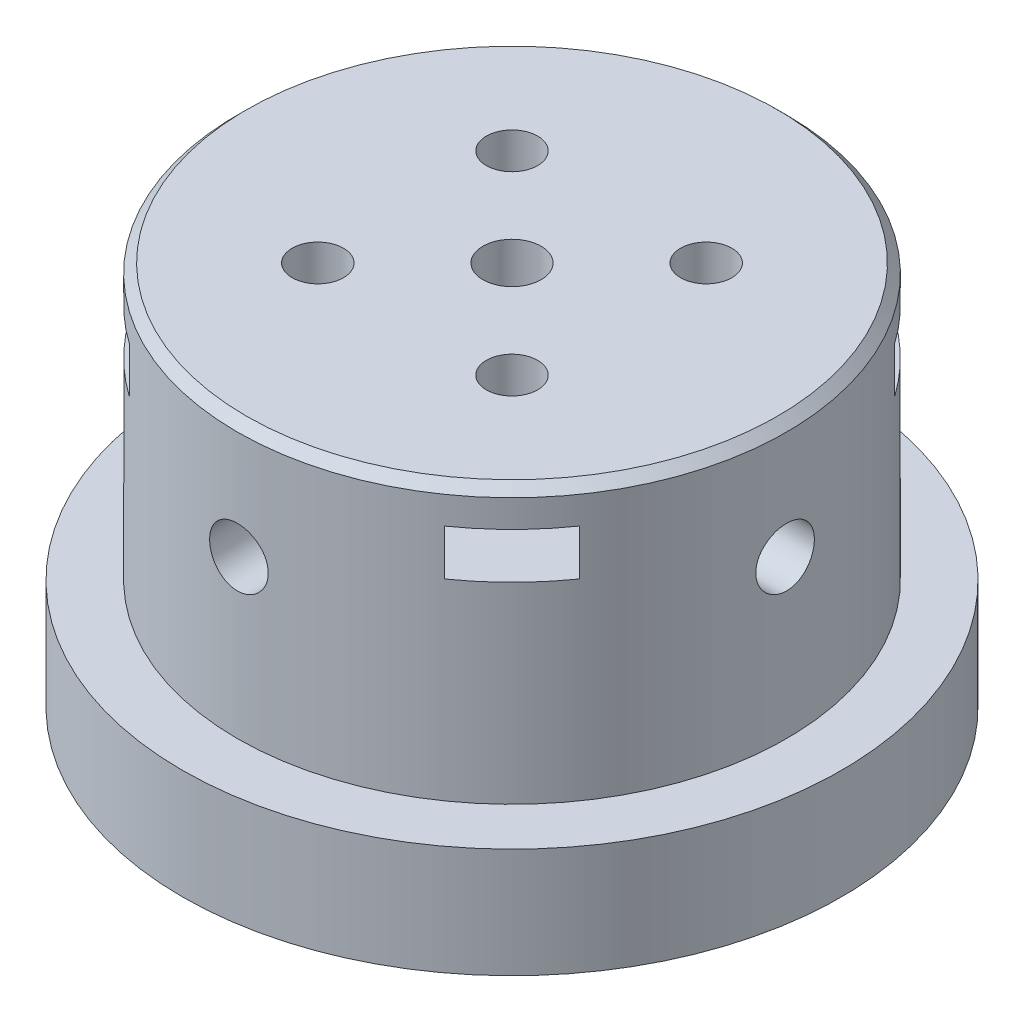
SolidWorks part; units mm, degrees
ref_plane "Front Plane" through (0, 0, 0) normal (0, 0, 1) x (1, 0, 0)
ref_plane "Top Plane" through (0, 0, 0) normal (0, 1, 0) x (1, 0, 0)
ref_plane "Right Plane" through (0, 0, 0) normal (1, 0, 0) x (0, 0, -1)
sketch "Sketch1" plane through (0, 0, 0) normal (0, 1, 0) x (1, 0, 0)
  circle A0 centre (0, 0) radius 15
  dimension "D1" = 30
extrude "Boss-Extrude1" add sketch "Sketch1" along normal blind 2
sketch "Sketch2" plane through (0, 2, 0) normal (0, 1, 0) x (1, 0, 0)
  circle A0 centre (0, 0) radius 13.5
  circle A1 centre (0, 0) radius 15
  circle A2 centre (0, 0) radius 15
  dimension "D1" = 0
  dimension "D2" = 1.5
extrude "Boss-Extrude2" add sketch "Sketch2" against normal up to surface (15 mm away)
sketch "Sketch3" plane through (0, -13, 0) normal (0, -1, 0) x (1, 0, 0)
  circle A0 centre (0, 0) radius 13.5 construction
  circle A1 centre (0, 0) radius 13.5
  circle A2 centre (0, 0) radius 18
  dimension "D1" = 36
extrude "Boss-Extrude3" add sketch "Sketch3" along normal up to surface (2 mm away)
sketch "Sketch4" plane through (0, -15, 0) normal (0, -1, 0) x (1, 0, 0)
  circle A0 centre (0, 0) radius 16.1
  circle A1 centre (0, 0) radius 18
  circle A2 centre (0, 0) radius 18
  dimension "D2" = 32.2
  dimension "D1" = 0
extrude "Boss-Extrude4" add sketch "Sketch4" along normal up to surface (3.9878 mm away)
chamfer "Chamfer1" distance 1 angle 45 1 edges at (0, -15, 13.5)
sketch "Sketch5" plane through (0, 2, 0) normal (0, 1, 0) x (1, 0, 0)
  circle A0 centre (0, 0) radius 13.5
  circle A1 centre (0, 0) radius 13.5 construction
extrude "Boss-Extrude5" add sketch "Sketch5" against normal up to surface (10.8258 mm away)
sketch "Sketch6" plane through (0, 2, 0) normal (0, 1, 0) x (1, 0, 0)
  circle A0 centre (0, 0) radius 1.5875
  dimension "D1" = 3.175
extrude "Cut-Extrude1" cut sketch "Sketch6" against normal through all both and the other way through all
sketch "Sketch7" plane through (0, 0, 0) normal (1, 0, 0) x (0, 0, -1)
  line L0 (0, 0) -> (0, -8.8258) construction
  line L1 (-1.5875, -8.8258) -> (1.5875, -8.8258) construction
  circle A0 centre (0, -4.4129) radius 1.6
  dimension "D1" = 3.2
extrude "Cut-Extrude2" cut sketch "Sketch7" against normal through all
ref_axis "Axis1" through (0, -14, 0) along (0, 1, 0)
ref_plane "Plane2" through (-10, 0, 0) normal (1, 0, 0) x (0, 0, -1)
ref_plane "Plane3" through (-9, 0, 0) normal (1, 0, 0) x (0, 0, -1)
sketch "Sketch11" plane through (-10, 0, 0) normal (1, 0, 0) x (0, 0, -1)
  circle A0 centre (0, -4.4129) radius 1.6 construction
  circle A1 centre (0, -4.4129) radius 1.6 construction
  circle A2 centre (0, -4.4129) radius 2
  dimension "D1" = 4
extrude "Cut-Extrude7" [suppressed] cut sketch "Sketch11" along normal blind 5.5
sketch "Sketch12" plane through (-10, 0, 0) normal (1, 0, 0) x (0, 0, -1)
  circle A0 centre (0, -4.4129) radius 3.5
  dimension "D1" = 7
extrude "Cut-Extrude8" [suppressed] cut sketch "Sketch12" against normal blind 5
chamfer "Chamfer2" [suppressed] distance 1 angle 45
pattern_circular "CirPattern3" count 4 over 360 about axis through (0, -14, 0) along (0, 1, 0) of "Cut-Extrude2", "Cut-Extrude7", "Cut-Extrude8", "Chamfer2"
sketch "Sketch13" plane through (-9, 0, 0) normal (1, 0, 0) x (0, 0, -1)
  line L0 (-2.75, -6.0006) -> (-2.75, -8.8258)
  line L1 (0, -7.5883) -> (2.75, -6.0006) construction
  line L2 (2.75, -6.0006) -> (2.75, -2.8252)
  line L3 (2.75, -2.8252) -> (0, -1.2375)
  line L4 (0, -1.2375) -> (-2.75, -2.8252)
  line L5 (-2.75, -2.8252) -> (-2.75, -6.0006)
  line L6 (-2.75, -6.0006) -> (0, -7.5883) construction
  line L7 (-2.75, -8.8258) -> (2.75, -8.8258)
  line L8 (2.75, -8.8258) -> (2.75, -6.0006)
  line L9 (-1.5875, -8.8258) -> (1.5875, -8.8258) construction
  circle A0 centre (0, -4.4129) radius 2.75 construction
  circle A1 centre (0, -4.4129) radius 1.6 construction
  dimension "D1" = 5.5
extrude "Cut-Extrude9" cut sketch "Sketch13" along normal blind 3
pattern_circular "CirPattern4" count 4 over 360 about axis through (0, -14, 0) along (0, 1, 0) of "Cut-Extrude9"
sketch "Sketch14" plane through (0, 2, 0) normal (0, -1, 0) x (1, 0, 0)
  line L0 (0, 0) -> (0, 13.5) construction
  line L1 (0, 0) -> (-9.5459, 9.5459) construction
  circle A0 centre (0, 0) radius 13.5 construction
  circle A1 centre (-5.3033, 5.3033) radius 1.4
  circle A2 centre (5.3033, 5.3033) radius 1.4
  circle A3 centre (5.3033, -5.3033) radius 1.4
  circle A4 centre (-5.3033, -5.3033) radius 1.4
  point P18 (0, 0)
  dimension "D3" = 2.8
  dimension "D1" = 45
  dimension "D2" = 7.5
  dimension "D4" = 4
extrude "Cut-Extrude10" cut sketch "Sketch14" along normal blind 4.5 and the other way through all
ref_plane "Plane4" through (0, 0, 0) normal (0, 1, 0) x (1, 0, 0)
sketch "Sketch15" plane through (0, 0, 0) normal (0, 1, 0) x (1, 0, 0)
  line L0 (0, 0) -> (-10.6066, 10.6066) construction
  line L1 (-8.2032, 4.5263) -> (-12.4451, 8.7681)
  line L2 (-7.4262, 7.4262) -> (-8.2032, 4.5263) construction
  line L3 (-8.2032, 4.5263) -> (-6.0803, 2.4034)
  line L4 (-6.0803, 2.4034) -> (-3.1804, 3.1804)
  line L5 (-3.1804, 3.1804) -> (-2.4034, 6.0803)
  line L6 (-2.4034, 6.0803) -> (-4.5263, 8.2032)
  line L7 (-4.5263, 8.2032) -> (-7.4262, 7.4262) construction
  line L8 (-12.4451, 8.7681) -> (-8.7681, 12.4451)
  line L9 (-8.7681, 12.4451) -> (-4.5263, 8.2032)
  line L10 (12.4451, 8.7681) -> (8.2032, 4.5263)
  line L11 (6.0803, 2.4034) -> (8.2032, 4.5263)
  line L12 (3.1804, 3.1804) -> (6.0803, 2.4034)
  line L13 (2.4034, 6.0803) -> (3.1804, 3.1804)
  line L14 (4.5263, 8.2032) -> (2.4034, 6.0803)
  line L15 (4.5263, 8.2032) -> (8.7681, 12.4451)
  line L16 (8.7681, 12.4451) -> (12.4451, 8.7681)
  line L17 (8.7681, -12.4451) -> (4.5263, -8.2032)
  line L18 (2.4034, -6.0803) -> (4.5263, -8.2032)
  line L19 (3.1804, -3.1804) -> (2.4034, -6.0803)
  line L20 (6.0803, -2.4034) -> (3.1804, -3.1804)
  line L21 (8.2032, -4.5263) -> (6.0803, -2.4034)
  line L22 (8.2032, -4.5263) -> (12.4451, -8.7681)
  line L23 (12.4451, -8.7681) -> (8.7681, -12.4451)
  line L24 (-12.4451, -8.7681) -> (-8.2032, -4.5263)
  line L25 (-6.0803, -2.4034) -> (-8.2032, -4.5263)
  line L26 (-3.1804, -3.1804) -> (-6.0803, -2.4034)
  line L27 (-2.4034, -6.0803) -> (-3.1804, -3.1804)
  line L28 (-4.5263, -8.2032) -> (-2.4034, -6.0803)
  line L29 (-4.5263, -8.2032) -> (-8.7681, -12.4451)
  line L30 (-8.7681, -12.4451) -> (-12.4451, -8.7681)
  circle A0 centre (0, 0) radius 15 construction
  circle A1 centre (-5.3033, 5.3033) radius 2.6 construction
  point P5 (-5.3033, 5.3033)
  point P41 (0, 0)
  dimension "D1" = 5.2
  dimension "D2" = 4
extrude "Cut-Extrude11" cut sketch "Sketch15" against normal blind 2.5
chamfer "Chamfer3" distance 0.5 angle 45 1 edges at (0, 2, 15)
sketch "Sketch16" plane through (0, -8.8258, 0) normal (0, -1, 0) x (1, 0, 0)
  line L0 (0, 0) -> (0, 18) construction
  line L1 (0, 0) -> (-12.7279, 12.7279) construction
  line L2 (-4.25, 4.25) -> (-4.25, 12.8136)
  line L3 (-2.75, 6) -> (-2.75, 9) construction
  line L4 (-4.25, 4.25) -> (-12.8136, 4.25)
  line L5 (4.25, 4.25) -> (12.8136, 4.25)
  line L6 (4.25, 4.25) -> (4.25, 12.8136)
  line L7 (4.25, -4.25) -> (4.25, -12.8136)
  line L8 (4.25, -4.25) -> (12.8136, -4.25)
  line L9 (-4.25, -4.25) -> (-12.8136, -4.25)
  line L10 (-4.25, -4.25) -> (-4.25, -12.8136)
  circle A0 centre (0, 0) radius 18 construction
  circle A1 centre (0, 0) radius 13.5 construction
  arc A2 (-12.8136, 4.25) -> (-4.25, 12.8136) centre (0, 0) cw
  arc A4 (4.25, 12.8136) -> (12.8136, 4.25) centre (0, 0) cw
  arc A5 (12.8136, -4.25) -> (4.25, -12.8136) centre (0, 0) cw
  arc A6 (-4.25, -12.8136) -> (-12.8136, -4.25) centre (0, 0) cw
  point P26 (0, 0)
  dimension "D1" = 45
  dimension "D2" = 1.5
  dimension "D3" = 4
extrude "Cut-Extrude12" cut sketch "Sketch16" against normal offset from surface (4.3258 mm away) 2 up to face at (-6.5434, -2.5, 6.5434)
